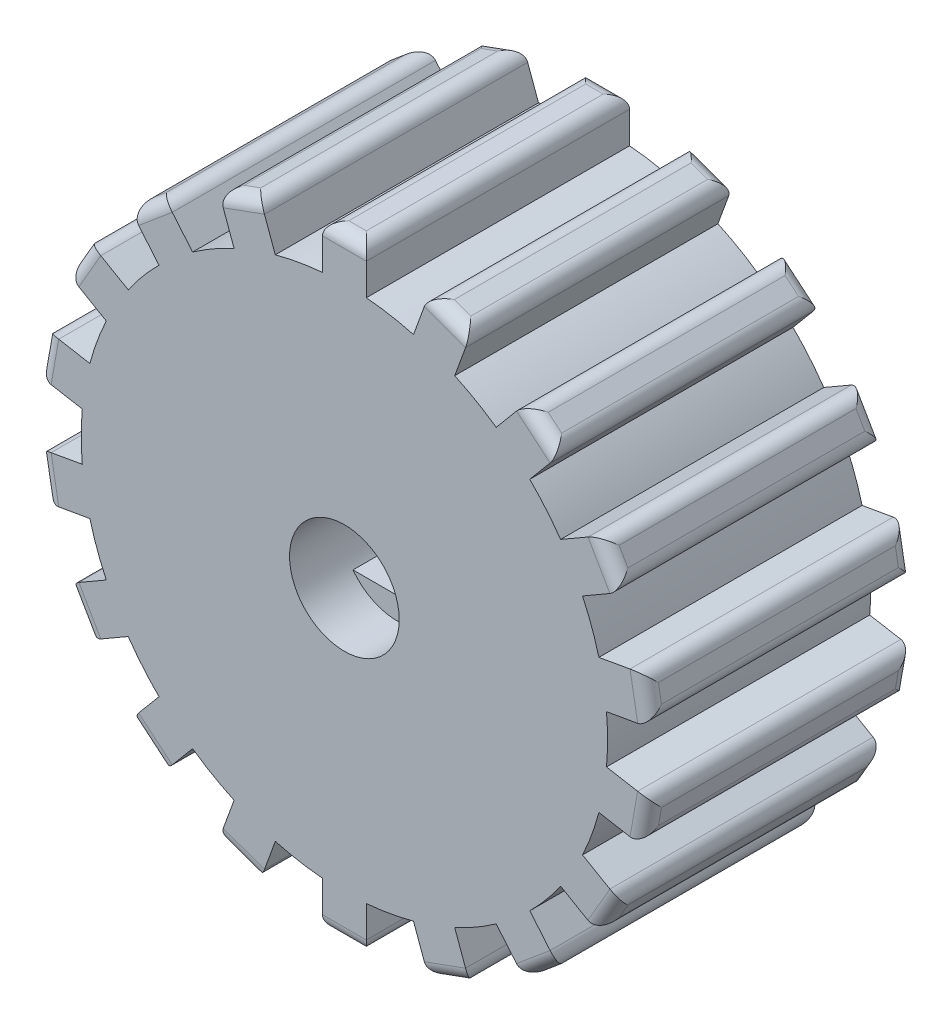
SolidWorks part; units mm, degrees
ref_plane "Front Plane" through (0, 0, 0) normal (0, 0, 1) x (1, 0, 0)
ref_plane "Top Plane" through (0, 0, 0) normal (0, 1, 0) x (1, 0, 0)
ref_plane "Right Plane" through (0, 0, 0) normal (1, 0, 0) x (0, 0, -1)
sketch "Sketch2" plane through (0, 0, 0) normal (0, 0, 1) x (1, 0, 0)
  circle A0 centre (0, 0) radius 60
extrude "Boss-Extrude1" add sketch "Sketch2" along normal blind 60
sketch "Sketch3" plane through (0, 0, 60) normal (0, 0, 1) x (1, 0, 0)
  line L0 (0, 60) -> (0, 70) construction
  line L1 (5, 70) -> (-5, 70)
  line L2 (-5, 70) -> (-5, 59.5215)
  line L3 (-5, 59.5215) -> (5, 59.5215)
  line L4 (5, 59.5215) -> (5, 70)
  circle A0 centre (0, 0) radius 60 construction
  point P9 (0, 70)
extrude "Boss-Extrude2" add sketch "Sketch3" against normal blind 60
fillet "Fillet2" radius 3 4 edges at (-5, 70, 30) (0, 70, 0) (5, 70, 30) (0, 70, 60)
pattern_circular "CirPattern1" count 18 over 360 about axis through (0, 0, 60) along (0, 0, -1) of "Fillet2", "Boss-Extrude2" reverse direction yes
sketch "Sketch4" plane through (0, 0, 60) normal (0, 0, 1) x (1, 0, 0)
  circle A0 centre (0, 0) radius 10
extrude "Cut-Extrude1" cut sketch "Sketch4" against normal blind 60
sketch "Sketch5" plane through (0, 0, 60) normal (0, 0, 1) x (1, 0, 0)
  circle A0 centre (0, 0) radius 22.4818
extrude "Boss-Extrude3" add sketch "Sketch5" against normal blind 60
sketch "Sketch6" plane through (0, 0, 60) normal (0, 0, 1) x (1, 0, 0)
  circle A0 centre (0, 0) radius 12.5
extrude "Cut-Extrude2" cut sketch "Sketch6" against normal blind 12
sketch "Sketch7" plane through (0, 0, 48) normal (0, 0, 1) x (1, 0, 0)
  line L1 (10.0373, -7.45) -> (-10.0373, -7.45)
  line L3 (10.0373, 7.45) -> (-10.0373, 7.45)
  arc A0 (-10.0373, 7.45) -> (-10.0373, -7.45) centre (0, 0) ccw
  arc A1 (10.0373, -7.45) -> (10.0373, 7.45) centre (0, 0) ccw
  point P0 (0, 0)
extrude "Cut-Extrude3" cut sketch "Sketch7" against normal blind 30.5
